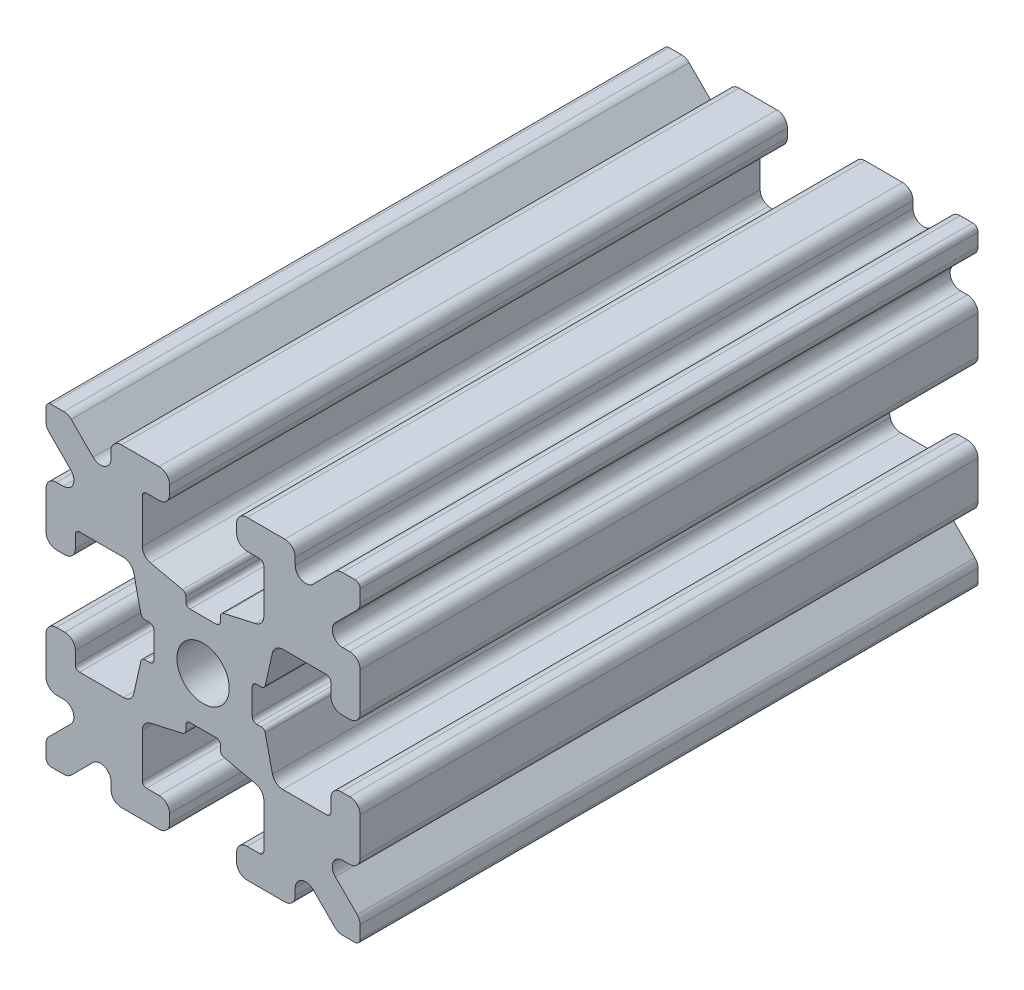
SolidWorks part; units mm, degrees
ref_plane "Front Plane" through (0, 0, 0) normal (0, 0, 1) x (1, 0, 0)
ref_plane "Top Plane" through (0, 0, 0) normal (0, 1, 0) x (1, 0, 0)
ref_plane "Right Plane" through (0, 0, 0) normal (1, 0, 0) x (0, 0, -1)
sketch "Sketch1" plane through (0, 0, 0) normal (0, 0, 1) x (1, 0, 0)
  line L1 (-7.5, -7.5) -> (7.5, -7.5)
  line L2 (-7.5, -7.5) -> (-7.5, 7.5)
  line L3 (-7.5, 7.5) -> (7.5, 7.5)
  line L4 (7.5, -7.5) -> (7.5, 7.5)
  line L5 (-7.5, -7.5) -> (7.5, 7.5) construction
  line L6 (-7.5, 7.5) -> (7.5, -7.5) construction
  circle A0 centre (0, 0) radius 1.25
  point P0 (0, 0)
  dimension "D2" = 2.5
  dimension "D1" = 15
extrude "Boss-Extrude1" add sketch "Sketch1" along normal mid plane 29.5
fillet "Fillet1" radius 0.25 4 edges at (7.5, -7.5, 0) (-7.5, -7.5, 0) (7.5, 7.5, 0) (-7.5, 7.5, 0)
sketch "Sketch2" plane through (0, 0, 14.75) normal (0, 0, 1) x (1, 0, 0)
  line L0 (-7.5, 7.25) -> (-7.5, -7.25) construction
  line L1 (-7.5, 1.6) -> (-6.1, 1.6)
  line L2 (-7.5, 1.6) -> (-7.5, -1.6)
  line L3 (-7.5, -1.6) -> (-6.1, -1.6)
  line L4 (-6.1, 1.6) -> (-6.1, 2.9)
  line L5 (0, 0) -> (-12.1036, 0) construction
  line L6 (-6.1, -2.9) -> (-3.4, -2.9)
  line L7 (0, 0) -> (-7.25, 7.25) construction
  line L8 (-6.1, 2.9) -> (-3.4, 2.9)
  line L9 (-3.4, -2.9) -> (-3.4, 2.9)
  line L10 (55, 0) -> (-55, 0) construction
  line L11 (-6.1, -2.9) -> (-6.1, -1.6)
  line L12 (2.9, 6.1) -> (1.6, 6.1)
  line L13 (2.9, 3.4) -> (-2.9, 3.4)
  line L14 (-2.9, 6.1) -> (-2.9, 3.4)
  line L15 (2.9, 6.1) -> (2.9, 3.4)
  line L16 (-1.6, 6.1) -> (-2.9, 6.1)
  line L17 (1.6, 7.5) -> (1.6, 6.1)
  line L18 (-1.6, 7.5) -> (1.6, 7.5)
  line L19 (-1.6, 7.5) -> (-1.6, 6.1)
  line L20 (-1.6, -7.5) -> (-1.6, -6.1)
  line L21 (-1.6, -7.5) -> (1.6, -7.5)
  line L22 (1.6, -7.5) -> (1.6, -6.1)
  line L23 (-1.6, -6.1) -> (-2.9, -6.1)
  line L24 (2.9, -6.1) -> (2.9, -3.4)
  line L25 (-2.9, -6.1) -> (-2.9, -3.4)
  line L26 (2.9, -3.4) -> (-2.9, -3.4)
  line L27 (2.9, -6.1) -> (1.6, -6.1)
  line L28 (6.1, -2.9) -> (6.1, -1.6)
  line L29 (3.4, -2.9) -> (3.4, 2.9)
  line L30 (6.1, 2.9) -> (3.4, 2.9)
  line L31 (6.1, -2.9) -> (3.4, -2.9)
  line L32 (6.1, 1.6) -> (6.1, 2.9)
  line L33 (7.5, -1.6) -> (6.1, -1.6)
  line L34 (7.5, 1.6) -> (7.5, -1.6)
  line L35 (7.5, 1.6) -> (6.1, 1.6)
  dimension "D1" = 3.2
  dimension "D2" = 5.8
  dimension "D3" = 1.4
  dimension "D4" = 2.7
extrude "Cut-Extrude1" cut sketch "Sketch2" against normal through all
sketch "Sketch4" plane through (0, 0, 14.75) normal (0, 0, 1) x (1, 0, 0)
  line L0 (-3.4, 2.9) -> (-2.75, 0)
  line L1 (55, 0) -> (-55, 0) construction
  line L2 (-2.75, 0) -> (-3.4, -2.9)
  line L3 (-3.4, -2.9) -> (-3.4, 2.9) construction
  line L4 (-3.4, 2.9) -> (-3.4, -2.9)
  line L5 (-2.9, 3.4) -> (0, 2.75)
  line L6 (0, 2.75) -> (2.9, 3.4)
  line L7 (2.9, 3.4) -> (-2.9, 3.4)
  line L8 (3.4, 2.9) -> (2.75, 0)
  line L9 (2.75, 0) -> (3.4, -2.9)
  line L10 (3.4, -2.9) -> (3.4, 2.9)
  line L11 (-2.9, -3.4) -> (0, -2.75)
  line L12 (0, -2.75) -> (2.9, -3.4)
  line L13 (2.9, -3.4) -> (-2.9, -3.4)
  circle A2 centre (0, 0) radius 2.75
  circle A3 centre (0, 0) radius 2.75 construction
  dimension "D1" = 1.5
extrude "Cut-Extrude3" cut sketch "Sketch4" against normal through all
fillet "Fillet3" radius 0.5 16 edges at (-6.1, -1.6, 0) (-7.5, -1.6, 0) (-6.1, 1.6, 0) (-7.5, 1.6, 0) (-1.6, -7.5, 0) (-1.6, -6.1, 0) (1.6, -7.5, 0) (1.6, -6.1, 0) (6.1, -1.6, 0) (7.5, -1.6, 0) (7.5, 1.6, 0) (6.1, 1.6, 0) (1.6, 7.5, 0) (1.6, 6.1, 0) (-1.6, 7.5, 0) (-1.6, 6.1, 0)
fillet "Fillet4" radius 0.5 8 edges at (-3.4, 2.9, 0) (-3.4, -2.9, 0) (2.9, -3.4, 0) (-2.9, -3.4, 0) (3.4, -2.9, 0) (3.4, 2.9, 0) (-2.9, 3.4, 0) (2.9, 3.4, 0)
fillet "Fillet5" radius 3 4 edges at (0, -2.75, 0) (2.75, 0, 0) (-2.75, 0, 0) (0, 2.75, 0)
fillet "Fillet6" radius 0.2 8 edges at (-2.9, -6.1, 0) (2.9, -6.1, 0) (6.1, -2.9, 0) (6.1, 2.9, 0) (2.9, 6.1, 0) (-2.9, 6.1, 0) (-6.1, -2.9, 0) (-6.1, 2.9, 0)
sketch "Sketch5" plane through (0, 0, 14.75) normal (0, 0, 1) x (1, 0, 0)
  line L0 (0, 0) -> (-7.25, 7.25) construction
  line L1 (-7.5, 6.4393) -> (-5.4607, 4.4)
  line L2 (-6.4393, 7.5) -> (-4.4, 5.4607)
  line L3 (-7.5, 4.4) -> (-5.4607, 4.4)
  line L4 (-3.8003, 2.9) -> (-5.9, 2.9) construction
  line L5 (0, 0) -> (-12.1819, 0) construction
  line L6 (-4.4, 7.5) -> (-4.4, 5.4607)
  line L7 (-2.9, 5.9) -> (-2.9, 3.8003) construction
  line L8 (-7.5, 6.4393) -> (-7.5, 4.4)
  line L9 (-7.5, 7.25) -> (-7.5, 2.1) construction
  line L10 (2.1, -7.5) -> (7.25, -7.5) construction
  line L11 (7.5, -7.25) -> (7.5, -2.1) construction
  line L12 (7.25, 7.5) -> (2.1, 7.5) construction
  line L13 (-2.1, 7.5) -> (-7.25, 7.5) construction
  line L14 (-4.4, 7.5) -> (-6.4393, 7.5)
  line L16 (55, 0) -> (-55, 0) construction
  line L17 (0, 0) -> (0, 10.993) construction
  line L18 (0, -54.6431) -> (0, 54.6431) construction
  line L20 (4.4, 7.5) -> (6.4393, 7.5)
  line L22 (7.5, 6.4393) -> (7.5, 4.4)
  line L23 (4.4, 7.5) -> (4.4, 5.4607)
  line L24 (7.5, 4.4) -> (5.4607, 4.4)
  line L25 (6.4393, 7.5) -> (4.4, 5.4607)
  line L26 (7.5, 6.4393) -> (5.4607, 4.4)
  line L27 (7.5, -6.4393) -> (5.4607, -4.4)
  line L28 (6.4393, -7.5) -> (4.4, -5.4607)
  line L29 (7.5, -4.4) -> (5.4607, -4.4)
  line L30 (4.4, -7.5) -> (4.4, -5.4607)
  line L31 (7.5, -6.4393) -> (7.5, -4.4)
  line L33 (4.4, -7.5) -> (6.4393, -7.5)
  line L36 (-4.4, -7.5) -> (-6.4393, -7.5)
  line L38 (-7.5, -6.4393) -> (-7.5, -4.4)
  line L39 (-4.4, -7.5) -> (-4.4, -5.4607)
  line L40 (-7.5, -4.4) -> (-5.4607, -4.4)
  line L41 (-6.4393, -7.5) -> (-4.4, -5.4607)
  line L42 (-7.5, -6.4393) -> (-5.4607, -4.4)
  dimension "D1" = 1.5
  dimension "D2" = 1.5
  dimension "D3" = 1.5
extrude "Cut-Extrude4" cut sketch "Sketch5" against normal through all
fillet "Fillet8" radius 0.5 24 edges at (-5.4607, 4.4, 0) (-7.5, 4.4, 0) (-5.4607, -4.4, 0) (-7.5, -4.4, 0) (-4.4, -7.5, 0) (-4.4, -5.4607, 0) (4.4, -7.5, 0) (4.4, -5.4607, 0) (5.4607, -4.4, 0) (7.5, -4.4, 0) (7.5, 4.4, 0) (5.4607, 4.4, 0) (4.4, 5.4607, 0) (4.4, 7.5, 0) (-4.4, 5.4607, 0) (-4.4, 7.5, 0) (-6.4393, 7.5, 0) (-7.5, 6.4393, 0) (6.4393, 7.5, 0) (7.5, 6.4393, 0) (6.4393, -7.5, 0) (7.5, -6.4393, 0) (-6.4393, -7.5, 0) (-7.5, -6.4393, 0)
sketch "Sketch6" plane through (0, 0, 14.75) normal (0, 0, 1) x (1, 0, 0)
  line L0 (0, 0) -> (0, 11.013) construction
  line L1 (0.6561, 2.8971) -> (2.1235, 2.8971) construction
  line L2 (0, -54.6431) -> (0, 54.6431) construction
  line L3 (0, 0) -> (7.25, 7.25) construction
  line L4 (7.5, 0.8255) -> (7.5, -0.8255)
  line L5 (2.3471, 0.8255) -> (7.5, 0.8255)
  line L6 (0, 0) -> (12.4016, 0) construction
  line L7 (0.8255, -7.5) -> (-0.8255, -7.5)
  line L8 (2.3471, -0.8255) -> (2.3471, 0.8255)
  line L9 (0.8255, -2.3471) -> (0.8255, -7.5)
  line L10 (7.5, -0.8255) -> (2.3471, -0.8255)
  line L11 (-7.5, -0.8255) -> (-2.3471, -0.8255)
  line L12 (-2.3471, -0.8255) -> (-2.3471, 0.8255)
  line L13 (-0.8255, -2.3471) -> (0.8255, -2.3471)
  line L14 (-0.8255, 7.5) -> (-0.8255, 2.3471)
  line L15 (-0.8255, 2.3471) -> (0.8255, 2.3471)
  line L16 (-0.8255, -7.5) -> (-0.8255, -2.3471)
  line L17 (0.8255, 2.3471) -> (0.8255, 7.5)
  line L18 (0.8255, 7.5) -> (-0.8255, 7.5)
  line L19 (3.9, 7.5) -> (2.1, 7.5) construction
  line L20 (-2.3471, 0.8255) -> (-7.5, 0.8255)
  line L21 (-7.5, 0.8255) -> (-7.5, -0.8255)
  point P5 (0, -2.5973)
  point P7 (0, 2.5973)
  dimension "D3" = 0.55
  dimension "D1" = 1.651
extrude "Cut-Extrude5" cut sketch "Sketch6" against normal through all
fillet "Fillet10" radius 0.2 16 edges at (-2.935, 0.8255, 0) (-2.935, -0.8255, 0) (2.935, -0.8255, 0) (2.935, 0.8255, 0) (0.8255, 2.935, 0) (-0.8255, 2.935, 0) (-2.3471, 0.8255, 0) (-2.3471, -0.8255, 0) (0.8255, 2.3471, 0) (-0.8255, 2.3471, 0) (2.3471, 0.8255, 0) (2.3471, -0.8255, 0) (0.8255, -2.935, 0) (0.8255, -2.3471, 0) (-0.8255, -2.3471, 0) (-0.8255, -2.935, 0)
